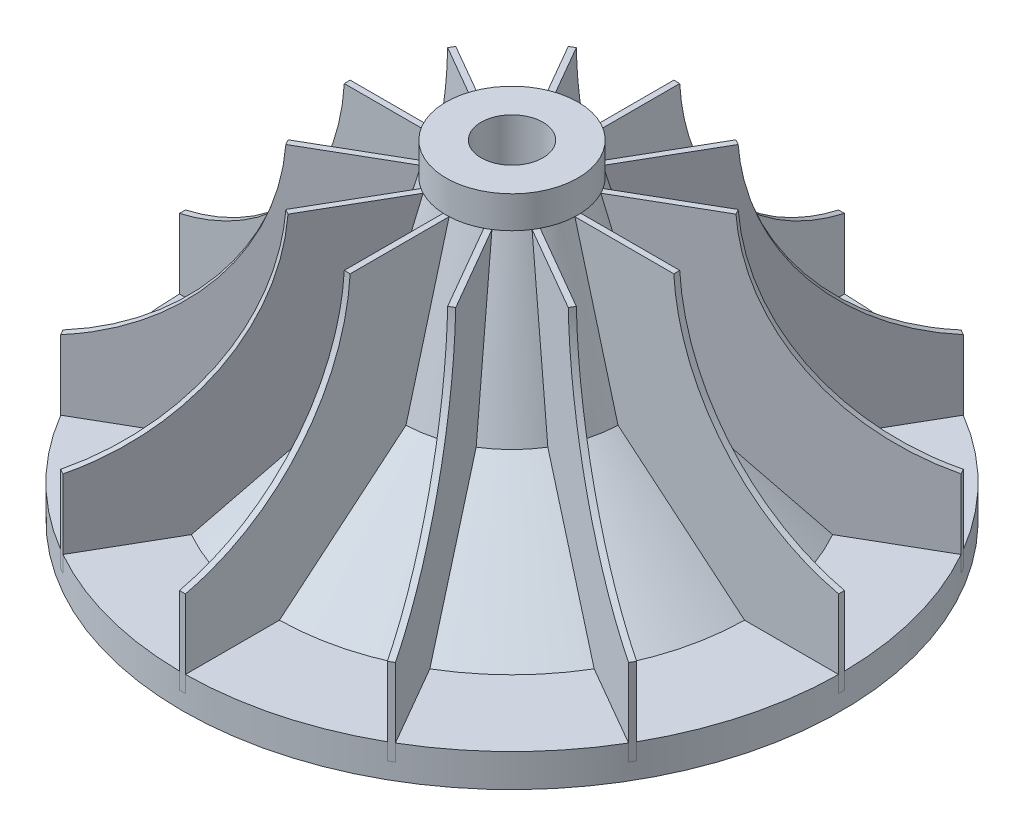
SolidWorks part; units mm, degrees
ref_plane "Front Plane" through (0, 0, 0) normal (0, 0, 1) x (1, 0, 0)
ref_plane "Top Plane" through (0, 0, 0) normal (0, 1, 0) x (1, 0, 0)
ref_plane "Right Plane" through (0, 0, 0) normal (1, 0, 0) x (0, 0, -1)
sketch "Sketch1" plane through (0, 0, 0) normal (0, 0, 1) x (1, 0, 0)
  line L7 (0, 0) -> (0, 37.1175) construction
  line L8 (0, 0) -> (-50.8, 0)
  line L9 (-50.8, 0) -> (-50.8, 5.08)
  line L10 (-36.306, 5.08) -> (-50.8, 5.08)
  line L11 (-36.306, 5.08) -> (-16.8028, 21.3522)
  line L12 (-16.8028, 21.3522) -> (-10.16, 45.8682)
  line L13 (-10.16, 45.8682) -> (-10.16, 50.8)
  line L14 (-10.16, 50.8) -> (0, 50.8)
  line L15 (0, 50.8) -> (0, 0)
  dimension "D1" = 50.8
  dimension "D2" = 10.16
  dimension "D3" = 50.8
  dimension "D4" = 5.08
  dimension "D5" = 25.4
  dimension "D6" = 25.4
  dimension "D7" = 215
revolve "Revolve1" add sketch "Sketch1" angle 360 about L7
ref_plane "Plane1" through (0, 50.8, 0) normal (0, 1, 0) x (1, 0, 0)
sketch "Sketch3" plane through (0, 50.8, 0) normal (0, 1, 0) x (1, 0, 0)
  line L6 (0.4559, -50.8) -> (0.4559, -8.89)
  line L7 (-0.4559, -50.8) -> (-0.4559, -8.89)
  line L8 (-0.4559, -8.89) -> (0.4559, -8.89)
  line L9 (-0.4559, -50.8) -> (0.4559, -50.8)
  dimension "D1" = 41.91
extrude "Boss-Extrude5" add sketch "Sketch3" against normal blind 48.26
pattern_circular "CirPattern8" count 12 over 360 about axis through (0, 5.08, 0) along (0, -1, 0) of "Boss-Extrude5"
sketch "Sketch4" plane through (0, 0, 0) normal (1, 0, 0) x (0, 0, -1)
  line L3 (-53.34, 58.5682) -> (-53.34, 15.3882)
  line L4 (-53.34, 15.3882) -> (-53.1322, 15.3882)
  line L5 (0, 0) -> (0, 72.6591) construction
  line L6 (-25.4, 45.8682) -> (-10.16, 45.8682)
  line L7 (-10.16, 45.8682) -> (-10.16, 51.0959)
  line L8 (-10.16, 51.0959) -> (-10.16, 59.6207)
  line L9 (-10.16, 59.6207) -> (-53.34, 58.5682)
  arc A0 (-53.1322, 15.3882) -> (-25.4, 45.8682) centre (-58.1589, 47.8177) ccw
  dimension "D1" = 43.18
  dimension "D2" = 10.16
revolve "Cut-Revolve1" cut sketch "Sketch4" angle 360 about L5
sketch "Sketch6" plane through (0, 50.8, 0) normal (0, 1, 0) x (1, 0, 0)
  circle A0 centre (0, 0) radius 4.7625
  dimension "D1" = 9.525
extrude "Cut-Extrude1" cut sketch "Sketch6" against normal up to next
equation "\"1.90n\"=2"
